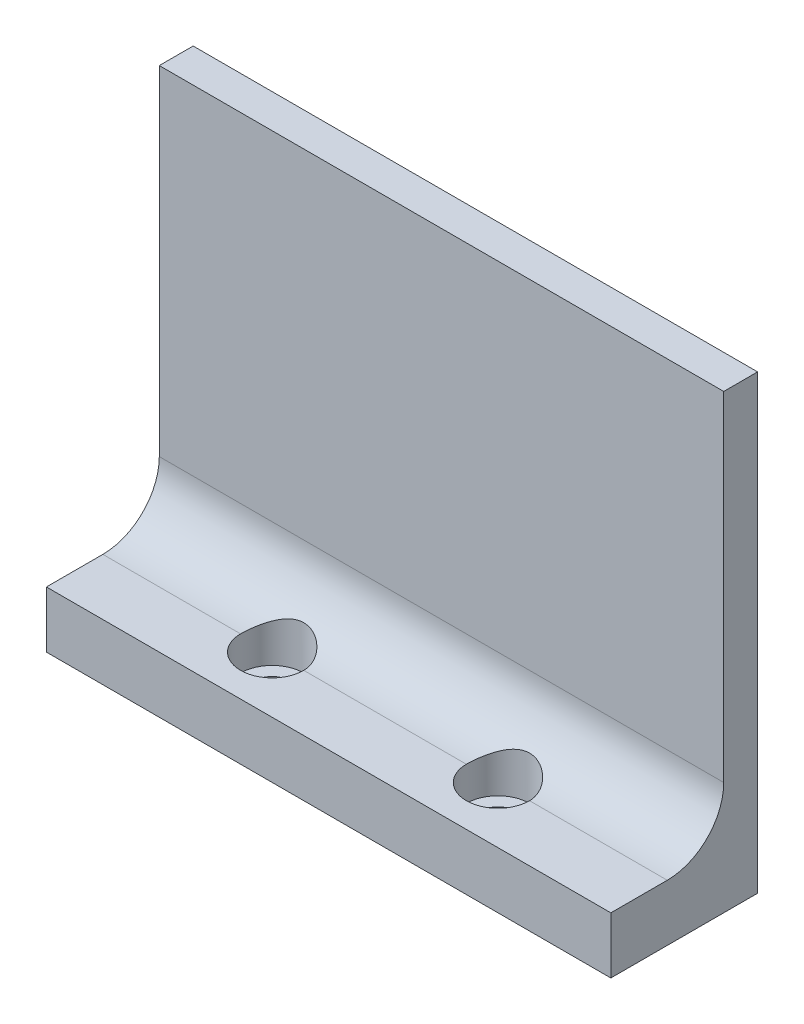
SolidWorks part; units mm, degrees
ref_plane "Alzado" through (0, 0, 0) normal (0, 0, 1) x (1, 0, 0)
ref_plane "Planta" through (0, 0, 0) normal (0, 1, 0) x (1, 0, 0)
ref_plane "Vista lateral" through (0, 0, 0) normal (1, 0, 0) x (0, 0, -1)
sketch "Croquis1" plane through (0, 0, 0) normal (0, 1, 0) x (1, 0, 0)
  line L0 (5, 5) -> (15, 5) construction
  line L1 (0, 0) -> (30, 0)
  line L2 (0, 0) -> (0, 10)
  line L3 (0, 10) -> (30, 10)
  line L4 (30, 0) -> (30, 10)
  line L5 (15, 5) -> (25, 5) construction
  line L6 (15, 5) -> (15, 10) construction
  circle A0 centre (5, 5) radius 1.6
  circle A1 centre (25, 5) radius 1.6
  dimension "D1" = 10
  dimension "D2" = 3.2
  dimension "D3" = 30
  dimension "D4" = 10
  dimension "D5" = 5
extrude "Saliente-Extruir1" add sketch "Croquis1" along normal blind 5
sketch "Croquis2" plane through (0, 5, 0) normal (0, 1, 0) x (1, 0, 0)
  circle A0 centre (5, 5) radius 2.8
  circle A1 centre (25, 5) radius 2.8
  dimension "D1" = 5.6
extrude "Cortar-Extruir1" cut sketch "Croquis2" against normal blind 3
sketch "Croquis3" plane through (0, 0, 0) normal (-1, 0, 0) x (0, 0, 1)
  line L1 (-10, 0) -> (-13, 0)
  line L2 (-10, 0) -> (-10, 40)
  line L3 (-10, 40) -> (-13, 40)
  line L4 (-13, 0) -> (-13, 40)
  dimension "D1" = 3
  dimension "D2" = 40
extrude "Saliente-Extruir2" add sketch "Croquis3" along normal blind 10 and the other way blind 30
sketch "Croquis4" plane through (0, 0, 0) normal (-1, 0, 0) x (0, 0, 1)
  line L4 (-10, 0) -> (0, 0)
  line L5 (0, 0) -> (0, 5)
  line L6 (0, 5) -> (-10, 5)
  line L7 (-10, 5) -> (-10, 0)
  line L8 (-10, 0) -> (0, 0)
  line L9 (0, 0) -> (0, 5)
  line L10 (0, 5) -> (-10, 5)
  line L11 (-10, 5) -> (-10, 0)
  dimension "D1" = 0
extrude "Saliente-Extruir3" add sketch "Croquis4" along normal blind 10
sketch "Croquis5" plane through (30, 0, 0) normal (1, 0, 0) x (0, 0, -1)
  line L4 (0, 0) -> (13, 0)
  line L5 (10, 40) -> (10, 5)
  line L6 (10, 5) -> (0, 5)
  line L7 (0, 5) -> (0, 0)
  line L8 (0, 0) -> (13, 0)
  line L9 (10, 40) -> (10, 5)
  line L10 (10, 5) -> (0, 5)
  line L11 (0, 5) -> (0, 0)
  line L14 (13, 0) -> (13, 40)
  line L15 (13, 0) -> (13, 40)
  line L16 (13, 40) -> (10, 40)
  line L17 (13, 40) -> (10, 40)
  dimension "D1" = 0
extrude "Saliente-Extruir4" add sketch "Croquis5" along normal blind 10
fillet "Redondeo1" radius 5 1 edges at (15, 5, -10)
